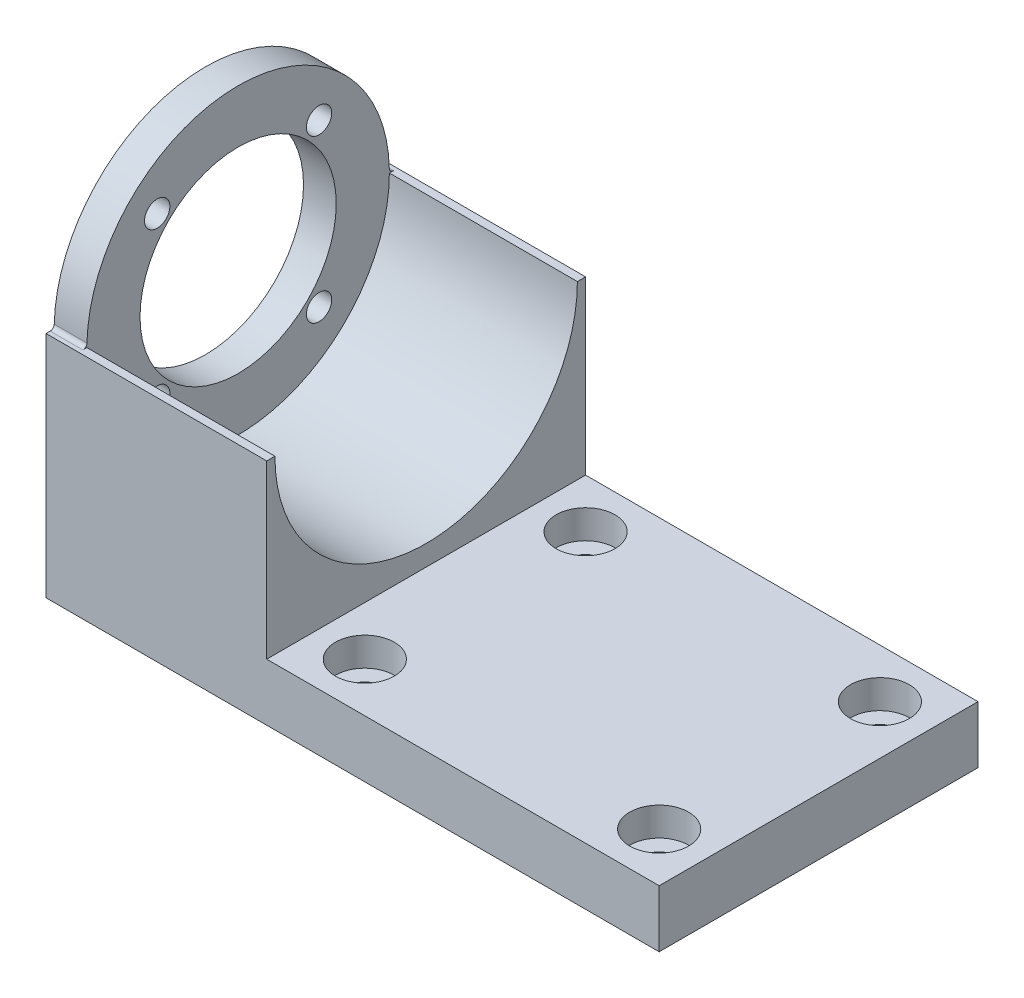
SolidWorks part; units mm, degrees
ref_plane "Plano frontal" through (0, 0, 0) normal (0, 0, 1) x (1, 0, 0)
ref_plane "Plano superior" through (0, 0, 0) normal (0, 1, 0) x (1, 0, 0)
ref_plane "Plano direito" through (0, 0, 0) normal (1, 0, 0) x (0, 0, -1)
sketch "Esboço1" plane through (0, 0, 0) normal (1, 0, 0) x (0, 0, -1)
  circle A0 centre (0, 0) radius 12
  circle A1 centre (0, 0) radius 18.5
  dimension "D1" = 24
  dimension "D2" = 37
extrude "Ressalto-extrusão1" add sketch "Esboço1" along normal blind 4
sketch "Esboço2" plane through (0, 0, 0) normal (-1, 0, 0) x (0, 0, 1)
  line L0 (-19.5, 0) -> (-19.5, -21)
  line L1 (-19.5, -21) -> (19.5, -21)
  line L2 (19.5, -21) -> (19.5, 0)
  line L5 (-19.5, 0) -> (-18.5, 0)
  line L6 (18.5, 0) -> (19.5, 0)
  arc A0 (-18.5, 0) -> (18.5, 0) centre (0, 0) ccw
  dimension "D2" = 37
  dimension "D1" = 39
  dimension "D3" = 21
  dimension "D4" = 1
extrude "Ressalto-extrusão2" add sketch "Esboço2" against normal blind 27
fillet "Filete1" radius 0.5 2 edges at (2, 0, 18.5) (2, 0, -18.5)
sketch "Esboço3" plane through (0, 0, 0) normal (-1, 0, 0) x (0, 0, 1)
  line L0 (19.5, -21) -> (19.5, 0) construction
  line L1 (-19.5, -21) -> (19.5, -21)
  line L2 (-19.5, -21) -> (-19.5, -28)
  line L3 (-19.5, -28) -> (19.5, -28)
  line L4 (19.5, -21) -> (19.5, -28)
  dimension "D1" = 7
extrude "Ressalto-extrusão3" add sketch "Esboço3" against normal blind 75
sketch "Esboço4" plane through (0, -21, 0) normal (0, 1, 0) x (1, 0, 0)
  line L0 (75, 19.5) -> (27, 19.5) construction
  line L1 (27, 19.5) -> (27, -19.5) construction
  circle A0 centre (33, 13.5) radius 1.55
  circle A1 centre (69, 13.5) radius 1.55
  circle A2 centre (33, -13.5) radius 1.55
  circle A3 centre (69, -13.5) radius 1.55
  dimension "D1" = 3.1
  dimension "D2" = 6
  dimension "D3" = 6
  dimension "D4" = 2
  dimension "D5" = 2
extrude "Corte-extrusão1" cut sketch "Esboço4" against normal up to surface (7 mm away) up to face at (37.5, -28, 0)
sketch "Esboço5" plane through (0, -21, 0) normal (0, 1, 0) x (1, 0, 0)
  circle A0 centre (33, 13.5) radius 3.6
  circle A1 centre (69, 13.5) radius 3.6
  circle A2 centre (69, -13.5) radius 3.6
  circle A3 centre (33, -13.5) radius 3.6
  dimension "D1" = 7.2
  dimension "D2" = 2
  dimension "D3" = 2
extrude "Corte-extrusão2" cut sketch "Esboço5" against normal blind 3.5
sketch "Esboço6" plane through (0, 0, 0) normal (-1, 0, 0) x (0, 0, 1)
  line L0 (0, 0) -> (23.4221, 0) construction
  line L1 (9.8995, 9.8995) -> (0, 0) construction
  circle A0 centre (9.8995, 9.8995) radius 1.55
  circle A1 centre (9.8995, -9.8995) radius 1.55
  circle A2 centre (-9.8995, -9.8995) radius 1.55
  circle A3 centre (-9.8995, 9.8995) radius 1.55
  point P14 (0, 0)
  dimension "D2" = 3.1
  dimension "D1" = 14
  dimension "D3" = 45
  dimension "D4" = 4
extrude "Corte-extrusão4" cut sketch "Esboço6" against normal up to surface (4 mm away) from surface up to face at (4, 0.0473, 0) starting at face at (0, -4.652, 0)
